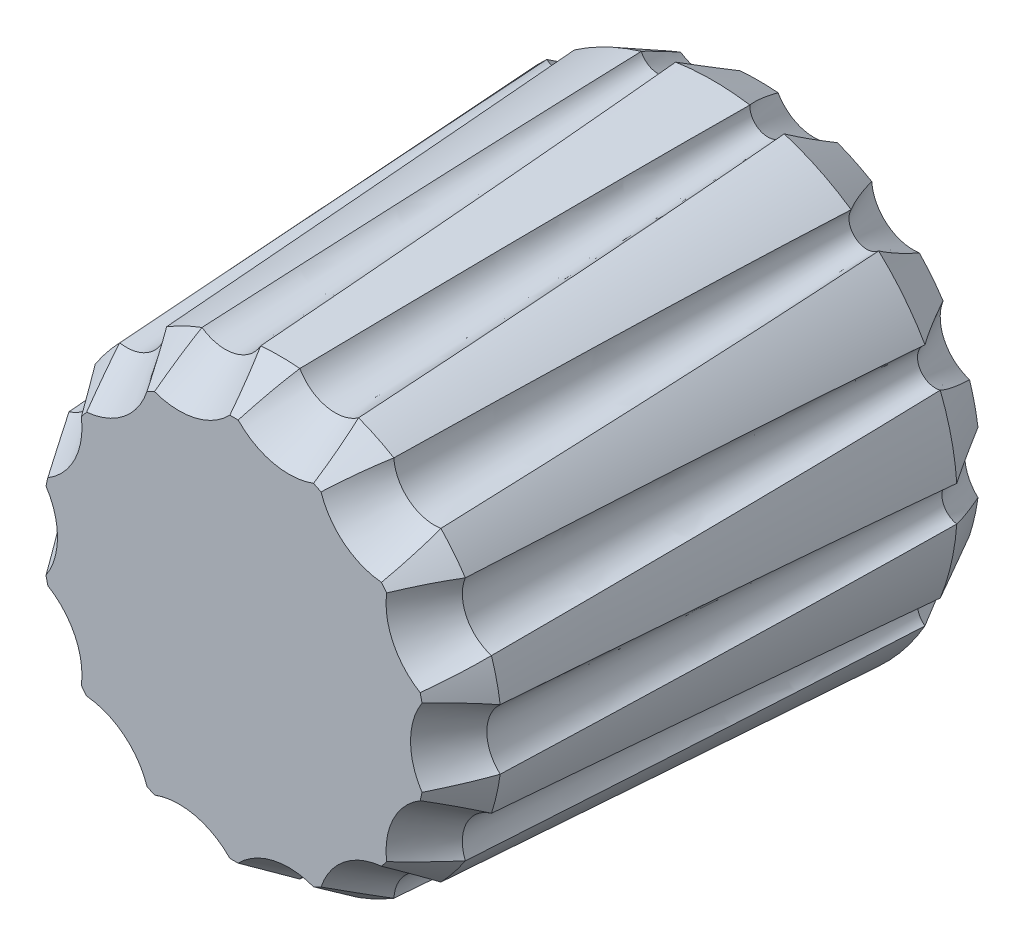
SolidWorks part; units mm, degrees
ref_plane "Plan de face" through (0, 0, 0) normal (0, 0, 1) x (1, 0, 0)
ref_plane "Plan de dessus" through (0, 0, 0) normal (0, 1, 0) x (1, 0, 0)
ref_plane "Plan de droite" through (0, 0, 0) normal (1, 0, 0) x (0, 0, -1)
sketch "Esquisse1" plane through (0, 0, 0) normal (0, 0, 1) x (1, 0, 0)
  line L0 (-13.0824, 0) -> (17.5938, 0) construction
  circle A0 centre (0, 0) radius 8
  circle A1 centre (-8, 0) radius 0.5
  circle A2 centre (-7.2078, 3.4711) radius 0.5
  circle A3 centre (-4.9879, 6.2547) radius 0.5
  circle A4 centre (-1.7802, 7.7994) radius 0.5
  circle A5 centre (1.7802, 7.7994) radius 0.5
  circle A6 centre (4.9879, 6.2547) radius 0.5
  circle A7 centre (7.2078, 3.4711) radius 0.5
  circle A8 centre (8, 0) radius 0.5
  circle A9 centre (7.2078, -3.4711) radius 0.5
  circle A10 centre (4.9879, -6.2547) radius 0.5
  circle A11 centre (1.7802, -7.7994) radius 0.5
  circle A12 centre (-1.7802, -7.7994) radius 0.5
  circle A13 centre (-4.9879, -6.2547) radius 0.5
  circle A14 centre (-7.2078, -3.4711) radius 0.5
  point P35 (0, 0)
  dimension "D1" = 16
  dimension "D2" = 1
  dimension "D3" = 14
extrude "Boss.-Extru.1" add sketch "Esquisse1" along normal blind 17 draft 3 contours A1 L0 A8 A0 A7 A6 A5 A4 A3 A2 | L0 A1 A0 A14 A13 A12 A11 A10 A9 A8 region at (0, -3.3535, 0) region at (0, 3.3535, 0)
chamfer "Chanfrein1" distance 1.5 angle 30 28 edges at (-7.7994, -1.7802, 0) (-6.7573, -3.2541, 0) (-6.2547, -4.9879, 0) (-4.6762, -5.8637, 0) (-3.4711, -7.2078, 0) (-1.6689, -7.312, 0) (0, -8, 0) (1.6689, -7.312, 0) (3.4711, -7.2078, 0) (4.6762, -5.8637, 0) (6.2547, -4.9879, 0) (6.7573, -3.2541, 0) (7.7994, -1.7802, 0) (7.5, 0, 0) (7.7994, 1.7802, 0) (6.7573, 3.2541, 0) (6.2547, 4.9879, 0) (4.6762, 5.8637, 0) (3.4711, 7.2078, 0) (1.6689, 7.312, 0) (0, 8, 0) (-1.6689, 7.312, 0) (-3.4711, 7.2078, 0) (-4.6762, 5.8637, 0) (-6.2547, 4.9879, 0) (-6.7573, 3.2541, 0) (-7.7994, 1.7802, 0) (-7.5, 0, 0) first distance on face at (-7.2002, -1.6434, 11.4306) first distance on face at (-6.4146, -3.0891, 11.4306) first distance on face at (-5.7741, -4.6047, 11.4306) first distance on face at (-4.439, -5.5663, 11.4306) first distance on face at (-3.2044, -6.654, 11.4306) first distance on face at (-1.5843, -6.9411, 11.4306) first distance on face at (0, -7.3854, 11.4306) first distance on face at (1.5843, -6.9411, 11.4306) first distance on face at (3.2044, -6.654, 11.4306) first distance on face at (4.439, -5.5663, 11.4306) first distance on face at (5.7741, -4.6047, 11.4306) first distance on face at (6.4146, -3.0891, 11.4306) first distance on face at (7.2002, -1.6434, 11.4306) first distance on face at (7.1196, 0, 11.4306) first distance on face at (7.2002, 1.6434, 11.4306) first distance on face at (6.4146, 3.0891, 11.4306) first distance on face at (5.7741, 4.6047, 11.4306) first distance on face at (4.439, 5.5663, 11.4306) first distance on face at (3.2044, 6.654, 11.4306) first distance on face at (1.5843, 6.9411, 11.4306) first distance on face at (0, 7.3854, 11.4306) first distance on face at (-1.5843, 6.9411, 11.4306) first distance on face at (-3.2044, 6.654, 11.4306) first distance on face at (-4.439, 5.5663, 11.4306) first distance on face at (-5.7741, 4.6047, 11.4306) first distance on face at (-6.4146, 3.0891, 11.4306) first distance on face at (-7.2002, 1.6434, 11.4306) first distance on face at (-7.1196, 0, 11.4306)
chamfer "Chanfrein2" distance 1.5 angle 30 28 edges at (-6.9308, 1.5819, 17) (-5.9546, 2.8676, 17) (-5.5581, 4.4324, 17) (-4.1207, 5.1672, 17) (-3.0845, 6.405, 17) (-1.4707, 6.4434, 17) (0, 7.1091, 17) (1.4707, 6.4434, 17) (3.0845, 6.405, 17) (4.1207, 5.1672, 17) (5.5581, 4.4324, 17) (5.9546, 2.8676, 17) (6.9308, 1.5819, 17) (6.6091, 0, 17) (6.9308, -1.5819, 17) (5.9546, -2.8676, 17) (5.5581, -4.4324, 17) (4.1207, -5.1672, 17) (3.0845, -6.405, 17) (1.4707, -6.4434, 17) (0, -7.1091, 17) (-1.4707, -6.4434, 17) (-3.0845, -6.405, 17) (-4.1207, -5.1672, 17) (-5.5581, -4.4324, 17) (-5.9546, -2.8676, 17) (-6.9308, -1.5819, 17) (-6.6091, 0, 17) first distance on face at (-7.1811, 1.639, 11.805) first distance on face at (-6.3969, 3.0806, 11.805) first distance on face at (-5.7588, 4.5925, 11.805) first distance on face at (-4.4268, 5.551, 11.805) first distance on face at (-3.1959, 6.6363, 11.805) first distance on face at (-1.5799, 6.922, 11.805) first distance on face at (0, 7.3657, 11.805) first distance on face at (1.5799, 6.922, 11.805) first distance on face at (3.1959, 6.6363, 11.805) first distance on face at (4.4268, 5.551, 11.805) first distance on face at (5.7588, 4.5925, 11.805) first distance on face at (6.3969, 3.0806, 11.805) first distance on face at (7.1811, 1.639, 11.805) first distance on face at (7.1, 0, 11.805) first distance on face at (7.1811, -1.639, 11.805) first distance on face at (6.3969, -3.0806, 11.805) first distance on face at (5.7588, -4.5925, 11.805) first distance on face at (4.4268, -5.551, 11.805) first distance on face at (3.1959, -6.6363, 11.805) first distance on face at (1.5799, -6.922, 11.805) first distance on face at (0, -7.3657, 11.805) first distance on face at (-1.5799, -6.922, 11.805) first distance on face at (-3.1959, -6.6363, 11.805) first distance on face at (-4.4268, -5.551, 11.805) first distance on face at (-5.7588, -4.5925, 11.805) first distance on face at (-6.3969, -3.0806, 11.805) first distance on face at (-7.1811, -1.639, 11.805) first distance on face at (-7.1, 0, 11.805)
sketch "Esquisse2" plane through (0, 0, 0) normal (0, 0, -1) x (-1, 0, 0)
  line L0 (1.6101, -1.1) -> (-1.6101, -1.1)
  circle A0 centre (0, 0) radius 1.95
  dimension "D1" = 3.9
  dimension "D2" = 1.1
extrude "Enlèv. mat.-Extru.1" cut sketch "Esquisse2" against normal blind 9 contours L0 A0 region at (0, 0.2776, 0)
extrude "Enlèv. mat.-Extru.2" cut sketch "Esquisse2<3>" against normal blind 2 contours L0 A0 region at (0, -1.4473, 0)
sketch "Esquisse2<3>" plane through (0, 0, 0) normal (0, 0, -1) x (-1, 0, 0) same geometry as "Esquisse2"
